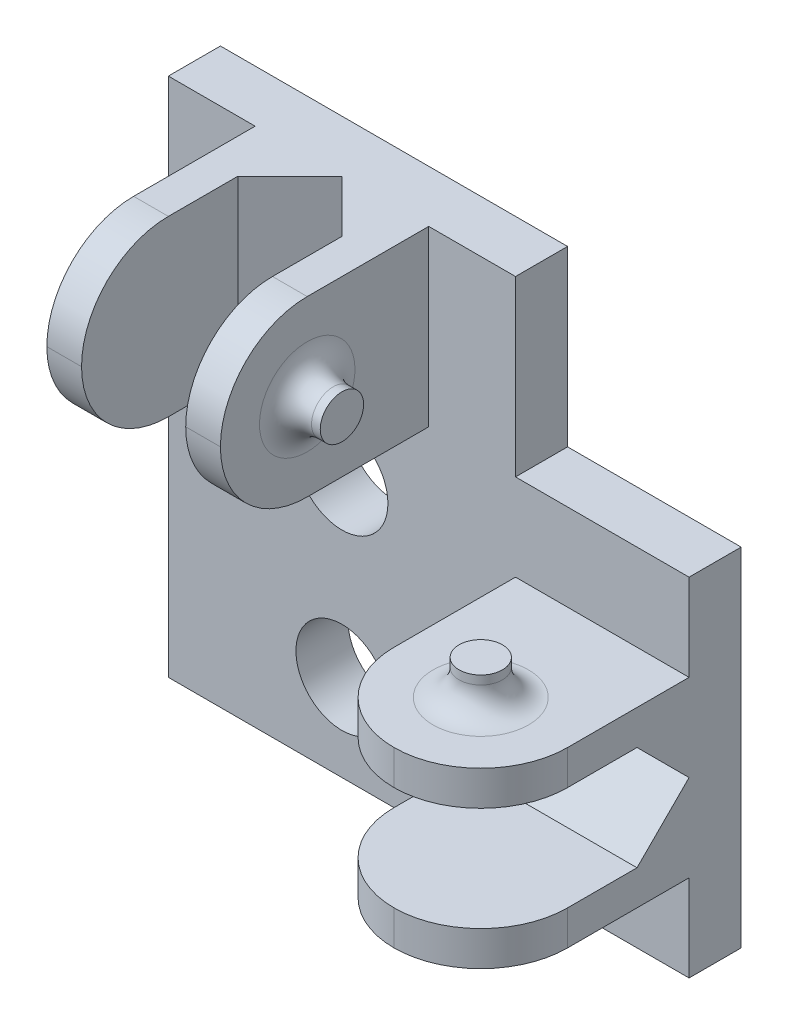
SolidWorks part; units mm, degrees
ref_plane "Front Plane" through (0, 0, 0) normal (0, 0, 1) x (1, 0, 0)
ref_plane "Top Plane" through (0, 0, 0) normal (0, 1, 0) x (1, 0, 0)
ref_plane "Right Plane" through (0, 0, 0) normal (1, 0, 0) x (0, 0, -1)
sketch "Sketch1" plane through (0, 0, 0) normal (0, 0, 1) x (1, 0, 0)
  line L1 (10, -15) -> (-10, -15)
  line L2 (10, -15) -> (10, 15)
  line L3 (10, 15) -> (-10, 15)
  line L4 (-10, -15) -> (-10, 15)
  line L5 (10, -15) -> (-10, 15) construction
  line L6 (10, 15) -> (-10, -15) construction
  line L7 (10, -15) -> (20, -15)
  line L8 (10, -15) -> (10, 5)
  line L9 (10, 5) -> (20, 5)
  line L10 (20, -15) -> (20, 5)
  circle A0 centre (0, -10) radius 2.65
  circle A1 centre (0, 0) radius 2.65
  point P0 (0, 0)
  dimension "D3" = 5.3
  dimension "D4" = 5.3
  dimension "D5" = 5
  dimension "D6" = 10
  dimension "D7" = 20
  dimension "D1" = 20
  dimension "D2" = 30
  dimension "D8" = 10
extrude "Boss-Extrude1" add sketch "Sketch1" along normal blind 3 contours L4 L1 L2 L3 A1 A0 | L7 L10 L9 L2 region at (0, -14.6394, 0) region at (15, -5, 0)
sketch "Sketch2" plane through (0, 0, 3) normal (0, 0, 1) x (1, 0, 0)
  line L0 (20, -15) -> (20, 5) construction
  line L1 (20, -10) -> (10, -10)
  line L2 (20, -10) -> (20, -8)
  line L3 (20, -8) -> (10, -8)
  line L4 (10, -10) -> (10, -8)
  line L5 (10, 15) -> (-10, 15) construction
  line L6 (20, 0) -> (10, 0)
  line L7 (20, 0) -> (20, -2)
  line L8 (20, -2) -> (10, -2)
  line L9 (10, 0) -> (10, -2)
  line L10 (5, 15) -> (3, 15)
  line L11 (5, 15) -> (5, 5)
  line L12 (5, 5) -> (3, 5)
  line L13 (3, 15) -> (3, 5)
  line L14 (-10, -15) -> (-10, 15) construction
  line L15 (-3, 15) -> (-5, 15)
  line L16 (-3, 15) -> (-3, 5)
  line L17 (-3, 5) -> (-5, 5)
  line L18 (-5, 15) -> (-5, 5)
  line L19 (20, -15) -> (-10, -15) construction
  dimension "D1" = 6
  dimension "D2" = 6
  dimension "D3" = 2
  dimension "D4" = 10
  dimension "D5" = 5
  dimension "D6" = 5
extrude "Boss-Extrude2" add sketch "Sketch2" along normal blind 12
fillet "Fillet1" radius 5 8 edges at (-4, 15, 15) (-4, 5, 15) (4, 15, 15) (4, 5, 15) (10, -1, 15) (20, -1, 15) (20, -9, 15) (10, -9, 15)
sketch "Sketch3" plane through (0, -10, 0) normal (0, -1, 0) x (1, 0, 0)
  circle A0 centre (15, 10) radius 1.25
  arc A1 (20, 10) -> (15, 15) centre (15, 10) ccw construction
  dimension "D1" = 2.5
extrude "Boss-Extrude3" add sketch "Sketch3" along normal blind 2
extrude "Boss-Extrude4" add sketch "Sketch3<2>" against normal blind 2 from offset 10 offset against normal yes
sketch "Sketch3<2>" plane through (0, -10, 0) normal (0, -1, 0) x (1, 0, 0) same geometry as "Sketch3"
sketch "Sketch4" plane through (5, 0, 0) normal (1, 0, 0) x (0, 0, -1)
  circle A0 centre (-10, 10) radius 1.25
  arc A1 (-10, 15) -> (-15, 10) centre (-10, 10) ccw construction
  dimension "D1" = 2.5
extrude "Boss-Extrude5" add sketch "Sketch4" along normal blind 2 contours A0
extrude "Boss-Extrude6" add sketch "Sketch4<3>" against normal blind 2 from offset 10 offset against normal yes
sketch "Sketch4<3>" plane through (5, 0, 0) normal (1, 0, 0) x (0, 0, -1) same geometry as "Sketch4"
fillet "Fillet2" radius 1.5 4 edges at (16.25, 0, 10) (13.75, -10, 10) (-5, 11.25, 10) (5, 8.75, 10)
chamfer "Chamfer1" distance 3 angle 45 4 edges at (15, -8, 3) (15, -2, 3) (-3, 10, 3) (3, 10, 3)
